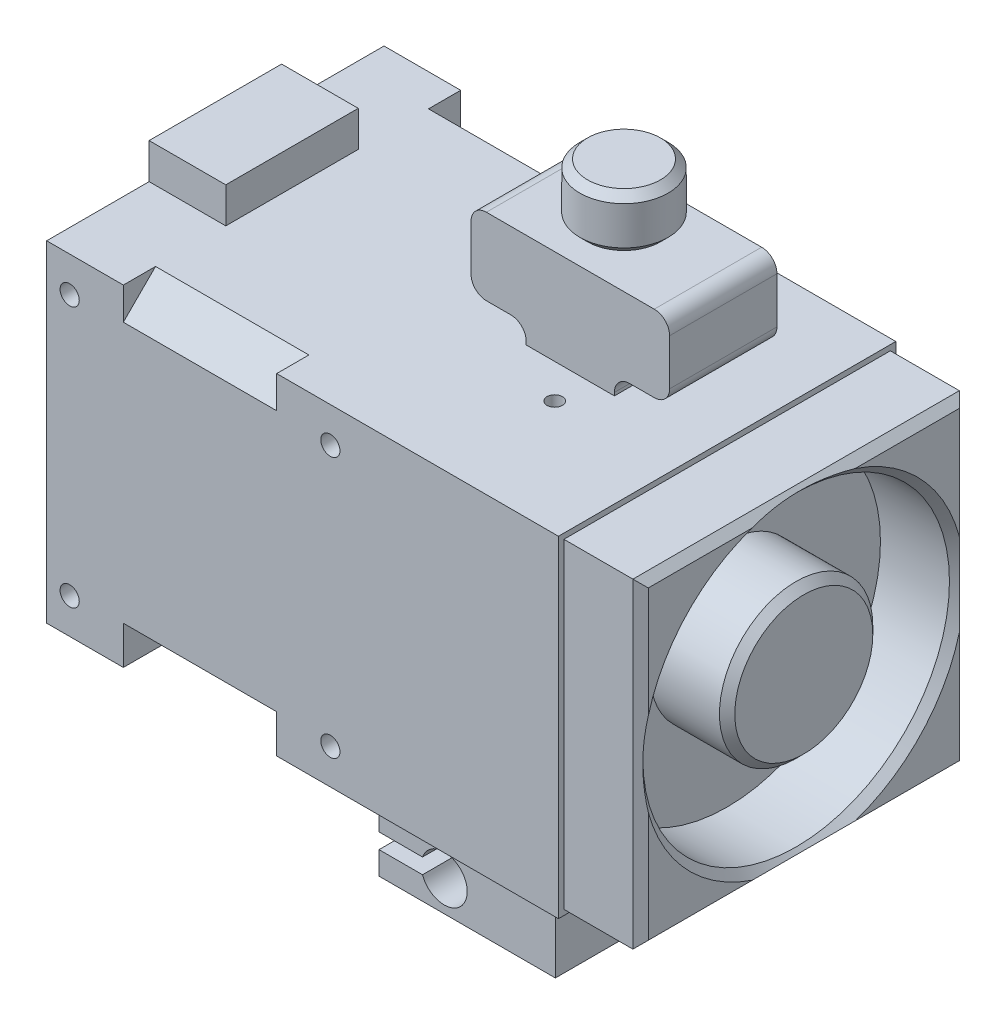
SolidWorks part; units mm, degrees
ref_plane "Front Plane" through (0, 0, 0) normal (0, 0, 1) x (1, 0, 0)
ref_plane "Top Plane" through (0, 0, 0) normal (0, 1, 0) x (1, 0, 0)
ref_plane "Right Plane" through (0, 0, 0) normal (1, 0, 0) x (0, 0, -1)
ref_plane "Nozzle Plane" through (0, 0, -15.1) normal (0, 0, 1) x (1, 0, 0)
ref_plane "Side Of Hemera" through (0, 0, -44) normal (0, 0, 1) x (1, 0, 0)
ref_plane "Hemera Rear" through (-3, 0, 0) normal (1, 0, 0) x (0, 0, -1)
ref_plane "Tension Arm Front Plane" through (0, 0, -19.5) normal (0, 0, 1) x (1, 0, 0)
ref_plane "Tension Arm Rear Plane" through (0, 0, -33.5) normal (0, 0, 1) x (1, 0, 0)
ref_plane "Tension knob plane" through (0, 0, -26.5) normal (0, 0, 1) x (1, 0, 0)
ref_plane "Motor Inset Start Plane" through (7, 0, 0) normal (1, 0, 0) x (0, 0, -1)
ref_plane "Motor Inset End Plane" through (27, 0, 0) normal (1, 0, 0) x (0, 0, -1)
sketch "Main Block Sketch" plane through (0, 0, 0) normal (0, 0, 1) x (1, 0, 0)
  line L0 (-3, -4.6) -> (73.75, -4.6)
  line L2 (-3, -4.6) -> (-3, 38.6)
  line L3 (-3, 38.6) -> (73.75, 38.6)
  line L5 (73.75, -4.6) -> (73.75, 38.6)
  line L6 (48.25, 38.6) -> (48.25, -4.6) construction
  point P0 (0, 0)
  point P5 (0, 34)
  point P6 (34, 34)
  point P8 (34, 0)
  dimension "D1" = 3
  dimension "D2" = 4.6
  dimension "D3" = 43.2
  dimension "D4" = 73.75
  dimension "D5" = 34
  dimension "D6" = 34
  dimension "D7" = 48.25
extrude "Main Block" add sketch "Main Block Sketch" against normal up to surface (44 mm away) up to plane "Side Of Hemera"
ref_plane "Fan Side Plane" through (73.75, 0, 0) normal (1, 0, 0) x (0, 0, -1)
sketch "Nozzle +Heatbreak Sketch" plane through (0, 0, -15.1) normal (0, 0, 1) x (1, 0, 0)
  line L0 (48.25, 38.6) -> (48.25, -4.6) construction
  line L1 (48.25, 38.6) -> (48.25, -4.6) construction
  line L2 (48.25, -11.7) -> (48.25, -23.5)
  line L3 (48.45, -24.2) -> (48.75, -24.2)
  line L4 (48.75, -24.2) -> (50.1504, -22.2)
  line L5 (50.1504, -22.2) -> (52.25, -22.2)
  line L6 (52.25, -22.2) -> (52.25, -19.2)
  line L7 (52.25, -19.2) -> (51.25, -19.2)
  line L8 (51.25, -19.2) -> (51.25, -11.7)
  line L9 (51.25, -11.7) -> (50.3, -11.7)
  line L10 (50.3, -11.7) -> (50.3, -4.6)
  line L12 (48.25, -4.6) -> (48.25, -11.7)
  line L13 (48.25, -3.6) -> (50.3, -3.6)
  line L14 (50.3, -3.6) -> (50.3, -4.6)
  line L15 (48.25, -3.6) -> (48.25, -4.6)
  line L16 (48.45, -24.2) -> (48.45, -23.5)
  line L17 (48.45, -23.5) -> (48.25, -23.5)
  dimension "D2" = 0.2
  dimension "D3" = 3
  dimension "D4" = 0.5
  dimension "D5" = 35
  dimension "D6" = 2
  dimension "D7" = 3
  dimension "D8" = 2.05
  dimension "D9" = 1
  dimension "D10" = 4
  dimension "D11" = 24.2
  dimension "D12" = 12.5
  dimension "D13" = 0.7
revolve "Nozzle+heatbreak" add sketch "Nozzle +Heatbreak Sketch" angle 360 about L1
sketch "Heater Block Sketch" plane through (0, 0, -15.1) normal (0, 0, 1) x (1, 0, 0)
  line L0 (48.25, 38.6) -> (48.25, -4.6) construction
  line L1 (48.25, 38.6) -> (48.25, -4.6) construction
  line L2 (38.9216, -13.6) -> (33.25, -13.6)
  line L3 (33.25, -7.1) -> (56.25, -7.1)
  line L4 (33.25, -7.1) -> (33.25, -13.6)
  line L5 (33.25, -18.6) -> (56.25, -18.6)
  line L6 (56.25, -7.1) -> (56.25, -18.6)
  line L7 (38.9216, -15.6) -> (33.25, -15.6)
  line L8 (33.25, -15.6) -> (33.25, -18.6)
  arc A0 (38.9216, -15.6) -> (38.9216, -13.6) centre (41.75, -14.6) ccw
  dimension "D4" = 2
  dimension "D6" = 3
  dimension "D1" = 8
  dimension "D2" = 23
  dimension "D3" = 11.5
  dimension "D5" = 14.5
  dimension "D7" = 4
  dimension "D8" = 14
extrude "Heater Block" add sketch "Heater Block Sketch" along normal mid plane 16
sketch "JST Connector Sketch" plane through (-3, 0, 0) normal (1, 0, 0) x (0, 0, -1)
  line L1 (0, 38.6) -> (0, -4.6) construction
  line L4 (0, 38.6) -> (13.36, 38.6) construction
  line L5 (13.36, 38.6) -> (30.64, 38.6)
  line L6 (13.36, 38.6) -> (13.36, 43.24)
  line L7 (13.36, 43.24) -> (30.64, 43.24)
  line L8 (30.64, 38.6) -> (30.64, 43.24)
  line L9 (30.64, 38.6) -> (44, 38.6) construction
  line L10 (44, 13.6459) -> (44, -13.6459) construction
  dimension "D1" = 13.36
  dimension "D2" = 4.64
extrude "JST Connector Block" add sketch "JST Connector Sketch" along normal blind 10
sketch "Idler Block Sketch" plane through (0, 0, -19.5) normal (0, 0, 1) x (1, 0, 0)
  line L0 (40.05, 38.6) -> (40.05, 41)
  line L1 (-3, 38.6) -> (73.75, 38.6) construction
  line L2 (40.05, 41) -> (32.85, 41)
  line L3 (32.85, 41) -> (32.85, 51)
  line L4 (32.85, 51) -> (58.75, 51)
  line L5 (58.75, 51) -> (58.75, 41)
  line L6 (58.75, 41) -> (51.55, 41)
  line L7 (51.55, 41) -> (51.55, 38.6)
  line L8 (40.05, 38.6) -> (51.55, 38.6)
  line L9 (40.05, 52) -> (51.55, 52) construction
  line L10 (45.8, 52) -> (45.8, 59) construction
  point P15 (45.8, 52)
  dimension "D1" = 15
  dimension "D2" = 12.4
  dimension "D3" = 10
  dimension "D4" = 11.5
  dimension "D5" = 7.2
  dimension "D6" = 7
  dimension "D7" = 11
extrude "Idler Block" add sketch "Idler Block Sketch" against normal up to surface (14 mm away) separate body up to plane "Tension Arm Rear Plane"
sketch "Filament Entrance Position Sketch" plane through (0, 0, -15.1) normal (0, 0, 1) x (1, 0, 0)
  point P0 (48.25, 38.6)
sketch "Tension knob sketch" plane through (0, 0, -26.5) normal (0, 0, 1) x (1, 0, 0)
  line L0 (46.8, 52) -> (46.8, 49)
  line L1 (45.8, 59) -> (51.55, 59)
  line L2 (45.8, 59) -> (45.8, 52)
  line L3 (46.8, 52) -> (51.55, 52)
  line L4 (51.55, 59) -> (51.55, 52)
  line L5 (46.8, 49) -> (45.8, 49)
  line L6 (45.8, 49) -> (45.8, 52)
  dimension "D1" = 3
  dimension "D2" = 1
revolve "Tension Knob" add sketch "Tension knob sketch" angle 360 about L2
combine bodies "Combination of Parts" operation type add bodies to combine 109 107 106 104 102
sketch "Motor Inset Cutout Sketch" plane through (7, 0, 0) normal (1, 0, 0) x (0, 0, -1)
  line L1 (5, 39.4) -> (39, 39.4)
  line L2 (-1, 40.4) -> (45, 40.4)
  line L3 (44, 34.4) -> (44, 0.4)
  line L4 (39, -4.6) -> (5, -4.6)
  line L5 (0, 0.4) -> (0, 34.4)
  line L6 (0, 34.4) -> (5, 39.4)
  line L7 (39, 39.4) -> (44, 34.4)
  line L8 (44, 0.4) -> (39, -4.6)
  line L9 (0, 0.4) -> (5, -4.6)
  line L10 (44, 22.5397) -> (44, -22.5397) construction
  line L11 (0, 38.6) -> (0, -4.6) construction
  line L12 (-1, 40.4) -> (-1, -5.6)
  line L13 (-1, -5.6) -> (45, -5.6)
  line L14 (45, 40.4) -> (45, -5.6)
  dimension "D1" = 45
  dimension "D2" = 5
  dimension "D3" = 1
  dimension "D4" = 1
  dimension "D5" = 1
extrude "Motor Inset" cut sketch "Motor Inset Cutout Sketch" along normal up to surface (20 mm away) up to plane "Motor Inset End Plane"
sketch "Fan Sketch" plane through (73.75, 0, 0) normal (1, 0, 0) x (0, 0, -1)
  line L0 (0, 38.6) -> (0, -4.6) construction
  line L1 (0, 38.6) -> (44, 38.6) construction
  line L2 (0, 38.6) -> (0, -4.6) construction
  line L3 (0, -4.6) -> (44, -4.6) construction
  line L4 (44, 38.6) -> (44, -4.6) construction
  line L5 (44, 22.5397) -> (44, -22.5397) construction
  line L6 (0, -4.6) -> (44, 38.6) construction
  line L8 (-3, -7.5455) -> (47, -7.5455) construction
  line L9 (-3, -7.5455) -> (-3, 41.5455) construction
  line L10 (-3, 41.5455) -> (47, 41.5455) construction
  line L11 (47, -7.5455) -> (47, 41.5455) construction
  line L12 (-3, -7.5455) -> (47, 41.5455) construction
  line L13 (-3, 41.5455) -> (47, -7.5455) construction
  line L14 (0.7136, -3.8994) -> (43.2864, -3.8994) construction
  line L15 (0.7136, -3.8994) -> (0.7136, 37.8994) construction
  line L16 (0.7136, 37.8994) -> (43.2864, 37.8994) construction
  line L17 (43.2864, -3.8994) -> (43.2864, 37.8994) construction
  line L18 (0.7136, -3.8994) -> (43.2864, 37.8994) construction
  line L19 (0.7136, 37.8994) -> (43.2864, -3.8994) construction
  circle A0 centre (22, 17) radius 10
  circle A1 centre (22, 17) radius 20
  dimension "D1" = 20
  dimension "D2" = 40
  dimension "D3" = 1
  dimension "D4" = 50
extrude "Main Fan Rotor Cut" cut sketch "Fan Sketch" against normal blind 10
sketch "Fan Edge Cut Sketch" plane through (73.75, 0, 0) normal (1, 0, 0) x (0, 0, -1)
  line L1 (-3, 41.5455) -> (47, 41.5455)
  line L2 (-3, 41.5455) -> (-3, -7.5455)
  line L3 (-3, -7.5455) -> (47, -7.5455)
  line L4 (47, 41.5455) -> (47, -7.5455)
  line L5 (43.2864, -3.8994) -> (0.7136, -3.8994)
  line L6 (43.2864, -3.8994) -> (43.2864, 37.8994)
  line L7 (43.2864, 37.8994) -> (0.7136, 37.8994)
  line L8 (0.7136, -3.8994) -> (0.7136, 37.8994)
extrude "Fan Housing Cut" cut sketch "Fan Edge Cut Sketch" against normal up to surface (10 mm away) up to face at (63.75, 17, -32)
hole_wizard "Mounting Holes Near Side" positions "Sketch11" profile "Sketch12" hole size "M3" standard "ISO"
sketch "Sketch11" plane through (0, 0, 0) normal (0, 0, 1) x (1, 0, 0)
  point P0 (0, 34)
  point P3 (0, 0)
  point P6 (34, 0)
  point P9 (34, 34)
sketch "Sketch12" plane through (0, 34, 0) normal (1, 0, 0) x (0, -1, 0)
  line L0 (0, 0) -> (0, 3.7511)
  line L1 (0, 3.7511) -> (1.25, 3)
  line L2 (1.25, 3) -> (1.25, 0)
  line L5 (1.25, 0) -> (0, 0)
  line L10 (0, 3.7511) -> (-1.25, 3) construction
  line L11 (0, -6.35) -> (0, 107.95) construction
  dimension "Hole Dia." = 2.5
  dimension "Hole Depth" = 3
  dimension "Drill Angle" = 118
hole_wizard "Mounting Holes Far Side" positions "Sketch13" profile "Sketch14" hole size "M3" standard "ISO"
sketch "Sketch13" plane through (0, 0, -44) normal (0, 0, 1) x (1, 0, 0)
  point P0 (0, 0)
  point P5 (34, 0)
  point P8 (34, 34)
  point P11 (0, 34)
sketch "Sketch14" plane through (0, 0, -44) normal (1, 0, 0) x (0, 1, 0)
  line L0 (0, 0) -> (0, 3.7511)
  line L1 (0, 3.7511) -> (1.25, 3)
  line L2 (1.25, 3) -> (1.25, 0)
  line L5 (1.25, 0) -> (0, 0)
  line L10 (0, 3.7511) -> (-1.25, 3) construction
  line L11 (0, -6.35) -> (0, 107.95) construction
  dimension "Hole Dia." = 2.5
  dimension "Hole Depth" = 3
  dimension "Drill Angle" = 118
hole_wizard "Filament Hole" positions "Sketch18" profile "Sketch19" hole size "Ø2.0" standard "ISO"
sketch "Sketch18" plane through (0, 38.6, 0) normal (0, 1, 0) x (1, 0, 0)
  point P0 (48.2283, 15.0297)
sketch "Sketch19" plane through (48.2283, 38.6, -15.0297) normal (1, 0, 0) x (0, 0, 1)
  line L0 (0, 0) -> (0, 10.6009)
  line L1 (0, 10.6009) -> (1, 10)
  line L2 (1, 10) -> (1, 0)
  line L5 (1, 0) -> (0, 0)
  line L10 (0, 10.6009) -> (-1, 10) construction
  line L11 (0, -6.35) -> (0, 107.95) construction
  dimension "Hole Dia." = 2
  dimension "Hole Depth" = 10
  dimension "Drill Angle" = 118
chamfer "Cosmetic Chamfers" distance 1 angle 45 9 edges at (73.75, 17, -32) (73.75, -3.8994, -22) (73.75, 17, -0.7136) (73.75, 37.8994, -22) (73.75, 17, -43.2864) (73.75, 17, -42) (48.25, -4.6, -17.15) (45.8, 59, -20.75) (45.8, 52, -20.75)
fillet "Tension Arm Fillets" radius 2 6 edges at (40.05, 41, -26.5) (51.55, 41, -26.5) (58.75, 41, -26.5) (58.75, 51, -26.5) (32.85, 41, -26.5) (32.85, 51, -26.5)
fillet "Nozzle Fillet" radius 0.2 1 edges at (47.75, -24.2, -15.1)
